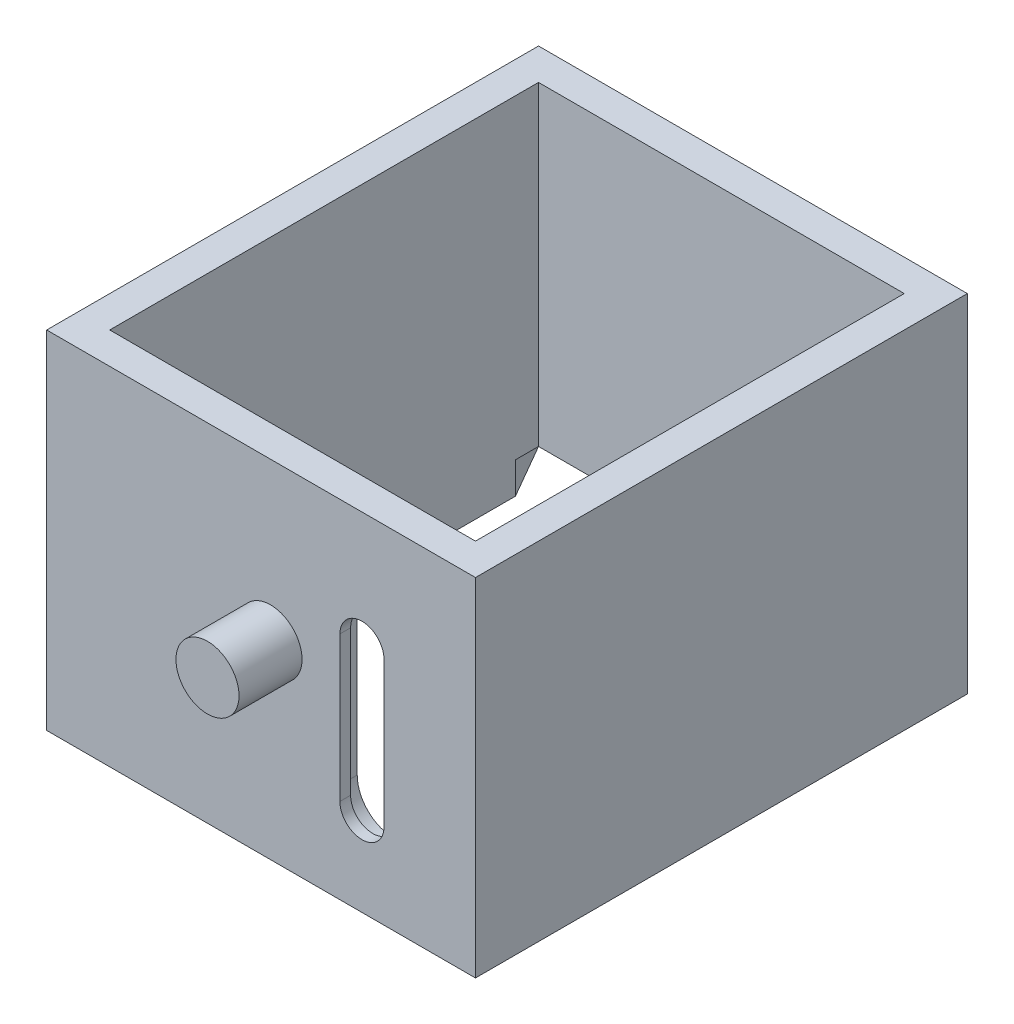
SolidWorks part; units mm, degrees
ref_plane "Ebene vorne" through (0, 0, 0) normal (0, 0, 1) x (1, 0, 0)
ref_plane "Ebene oben" through (0, 0, 0) normal (0, 1, 0) x (1, 0, 0)
ref_plane "Ebene rechts" through (0, 0, 0) normal (1, 0, 0) x (0, 0, -1)
sketch "Skizze1" plane through (0, 0, 0) normal (0, 0, 1) x (1, 0, 0)
  line L1 (-68, 55) -> (0, 55)
  line L2 (-68, 55) -> (-68, 0)
  line L3 (-68, 0) -> (0, 0)
  line L4 (0, 55) -> (0, 0)
  line L5 (-68, 55) -> (0, 0) construction
  line L6 (-68, 0) -> (0, 55) construction
  point P0 (-34, 27.5)
  dimension "68" = 68
  dimension "D2" = 55
extrude "Aufsatz-Linear austragen1" add sketch "Skizze1" along normal blind 78
sketch "Skizze2" plane through (0, 55, 0) normal (0, 1, 0) x (1, 0, 0)
  line L0 (-68, -78) -> (-68, 0) construction
  line L1 (-63, -5) -> (-5, -5)
  line L2 (-63, -5) -> (-63, -73)
  line L3 (-63, -73) -> (-5, -73)
  line L4 (-5, -5) -> (-5, -73)
  line L5 (0, 0) -> (-68, 0) construction
  line L6 (0, -78) -> (0, 0) construction
  line L7 (0, -78) -> (-68, -78) construction
  dimension "D1" = 5
  dimension "D2" = 5
  dimension "D3" = 5
  dimension "D4" = 5
extrude "Schnitt-Linear austragen1" cut sketch "Skizze2" against normal through all
sketch "Skizze3" plane through (0, 0, 78) normal (0, 0, 1) x (1, 0, 0)
  line L0 (0, 55) -> (-68, 55) construction
  line L2 (0, 0) -> (0, 55) construction
  circle A0 centre (-32.5, 30) radius 5
  dimension "D1" = 10
  dimension "D2" = 25
  dimension "D3" = 32.5
extrude "Aufsatz-Linear austragen2" add sketch "Skizze3" along normal blind 10
hole_wizard "Stirnsenkung Langloch für M6 Senkschraube (Kopf Button)1" positions "Skizze14" profile "Skizze13" size "M6" standard "ANSI Metrisch" slot yes end condition up to next
sketch "Skizze14" plane through (0, 0, 73) normal (0, 0, -1) x (-1, 0, 0)
  line L0 (18, 10) -> (18, 40) construction
  line L3 (68, 55) -> (68, 0) construction
  line L4 (68, 0) -> (0, 0) construction
  point P0 (18, 25)
  dimension "D1" = 30
  dimension "D2" = 50
  dimension "D3" = 10
sketch "Skizze13" plane through (-18, 25, 73) normal (1, 0, 0) x (0, 1, 0)
  line L0 (0, 0) -> (0, 5)
  line L1 (0, 5) -> (3.5, 5)
  line L3 (3.5, 5) -> (3.5, 3.3)
  line L4 (3.5, 3.3) -> (5.75, 3.3)
  line L5 (5.75, 3.3) -> (5.75, 0)
  line L7 (5.75, 0) -> (0, 0)
  line L11 (0, -6.35) -> (0, 107.95) construction
  dimension "Bohrerdurchmesser" = 7
  dimension "Bohrungstiefe" = 5
  dimension "Senkdurchmesser2" = 11.5
  dimension "Senktiefe2" = 3.3
sketch "Skizze15" plane through (0, 0, 0) normal (0, -1, 0) x (1, 0, 0)
  line L0 (0, 0) -> (-5, 8.6603)
  line L1 (-5, 73) -> (-5, 5) construction
  line L2 (-5, 8.6603) -> (-63, 8.6603)
  line L3 (-63, 5) -> (-63, 73) construction
  line L4 (-63, 8.6603) -> (-68, 0)
  line L5 (-68, 0) -> (0, 0)
  dimension "D1" = 10
extrude "Schnitt-Linear austragen2" cut sketch "Skizze15" against normal blind 5
